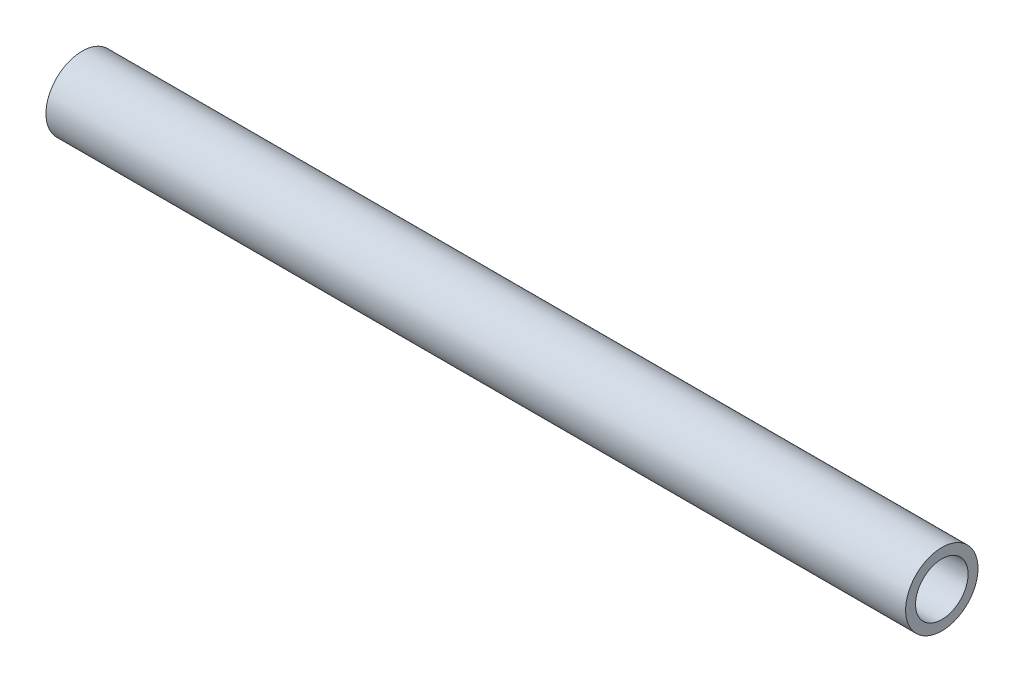
SolidWorks part; units mm, degrees
ref_plane "Front Plane" through (0, 0, 0) normal (0, 0, 1) x (1, 0, 0)
ref_plane "Top Plane" through (0, 0, 0) normal (0, 1, 0) x (1, 0, 0)
ref_plane "Right Plane" through (0, 0, 0) normal (1, 0, 0) x (0, 0, -1)
sketch "Sketch1" plane through (0, 0, 0) normal (1, 0, 0) x (0, 0, -1)
  circle A0 centre (0, 0) radius 13.15
  circle A1 centre (0, 0) radius 9.55
  dimension "D1" = 26.3
  dimension "D2" = 19.1
extrude "Boss-Extrude1" add sketch "Sketch1" along normal blind 312.4
